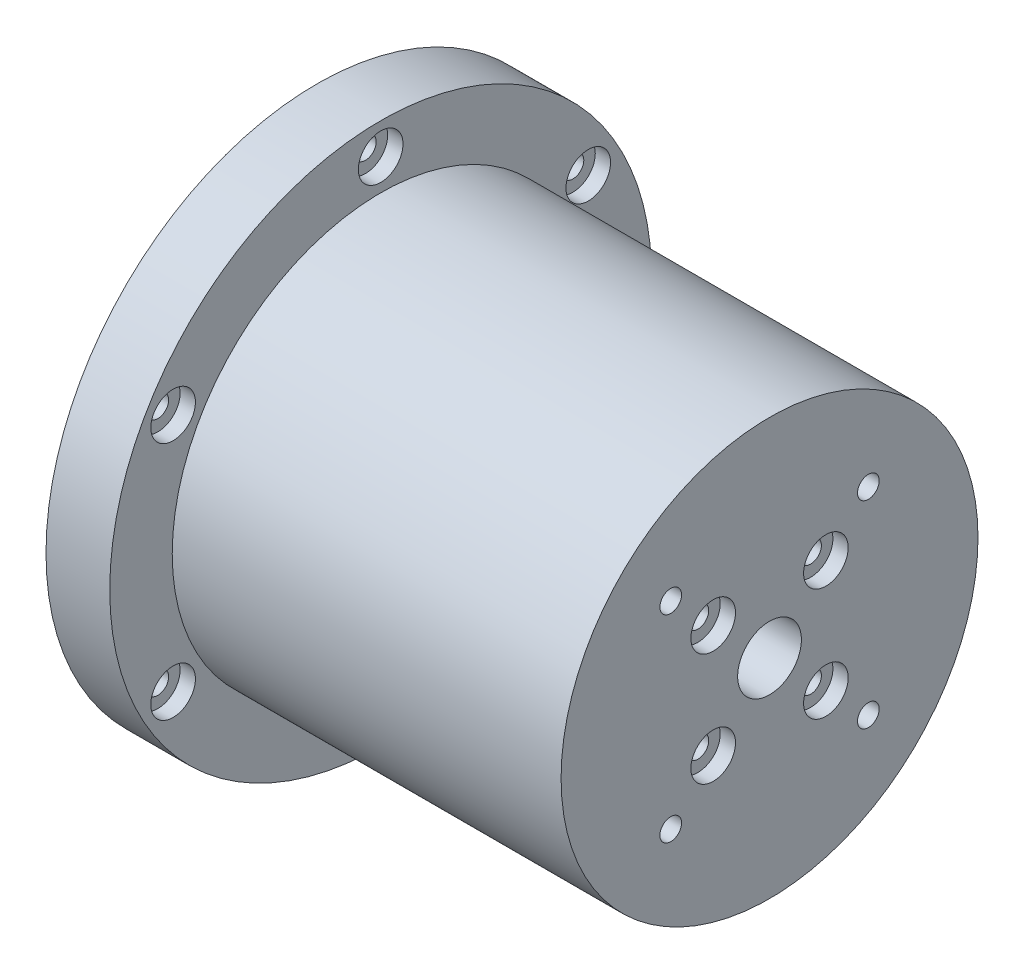
SolidWorks part; units mm, degrees
material "ABS"
ref_plane "Front" through (0, 0, 0) normal (0, 0, 1) x (1, 0, 0)
ref_plane "Top" through (0, 0, 0) normal (0, 1, 0) x (1, 0, 0)
ref_plane "Right" through (0, 0, 0) normal (1, 0, 0) x (0, 0, -1)
sketch "Croquis1" plane through (0, 0, 0) normal (1, 0, 0) x (0, 0, -1)
  circle A0 centre (0, 0) radius 32.7
  circle A1 centre (0, 0) radius 5
  dimension "D1" = 65.4
  dimension "D2" = 10
extrude "Saliente-Extruir1" add sketch "Croquis1" along normal mid plane 8.5
hole_wizard "Refrentado para tornillo con cabeza troncocónica de M31" positions "Croquis2" profile "Croquis4" counterbore size "M3" standard "Ansi Metric" end condition up to next
sketch "Croquis2" plane through (4.25, 0, 0) normal (1, 0, 0) x (0, 0, -1)
  line L1 (-8.8388, -8.8388) -> (8.8388, -8.8388) construction
  line L2 (-8.8388, -8.8388) -> (-8.8388, 8.8388) construction
  line L3 (-8.8388, 8.8388) -> (8.8388, 8.8388) construction
  line L4 (8.8388, -8.8388) -> (8.8388, 8.8388) construction
  line L5 (-8.8388, -8.8388) -> (8.8388, 8.8388) construction
  line L6 (-8.8388, 8.8388) -> (8.8388, -8.8388) construction
  point P2 (8.8388, 8.8388)
  point P25 (-8.8388, -8.8388)
  point P26 (-8.8388, 8.8388)
  point P27 (8.8388, -8.8388)
  dimension "D1" = 25
sketch "Croquis4" plane through (4.25, 8.8388, -8.8388) normal (0, 1, 0) x (0, 0, -1)
  line L0 (0, 0) -> (0, 8.5)
  line L1 (0, 8.5) -> (1.7, 8.5)
  line L3 (1.7, 8.5) -> (1.7, 2.4)
  line L4 (1.7, 2.4) -> (3.5, 2.4)
  line L5 (3.5, 2.4) -> (3.5, 0)
  line L7 (3.5, 0) -> (0, 0)
  line L11 (0, -6.35) -> (0, 107.95) construction
  dimension "Diámetro de taladro hasta el siguiente" = 3.4
  dimension "Profundidad de taladro hasta el siguiente" = 8.5
  dimension "Diámetro de refrentado" = 7
  dimension "Profundidad de refrentado" = 2.4
sketch "Croquis5" plane through (-4.25, 0, 0) normal (-1, 0, 0) x (0, 0, 1)
  circle A0 centre (0, 0) radius 21.5
  circle A1 centre (0, 0) radius 32.7 construction
  circle A2 centre (0, 0) radius 32.7
  dimension "D1" = 43
extrude "Saliente-Extruir2" add sketch "Croquis5" along normal blind 55
hole_wizard "Taladro de margen para M31" positions "Croquis6" profile "Croquis8" hole size "M3" standard "Ansi Metric"
sketch "Croquis6" plane through (-59.25, 0, 0) normal (-1, 0, 0) x (0, 0, 1)
  line L1 (-17.075, -17.075) -> (17.075, -17.075) construction
  line L2 (-17.075, -17.075) -> (-17.075, 17.075) construction
  line L3 (-17.075, 17.075) -> (17.075, 17.075) construction
  line L4 (17.075, -17.075) -> (17.075, 17.075) construction
  line L5 (-17.075, -17.075) -> (17.075, 17.075) construction
  line L6 (-17.075, 17.075) -> (17.075, -17.075) construction
  point P2 (17.075, 17.075)
  point P25 (-17.075, -17.075)
  point P26 (-17.075, 17.075)
  point P27 (17.075, -17.075)
  dimension "D1" = 34.15
sketch "Croquis8" plane through (-59.25, 17.075, 17.075) normal (0, 1, 0) x (0, 0, 1)
  line L0 (0, 0) -> (0, 16.0215)
  line L1 (0, 16.0215) -> (1.7, 15)
  line L2 (1.7, 15) -> (1.7, 0)
  line L5 (1.7, 0) -> (0, 0)
  line L10 (0, 16.0215) -> (-1.7, 15) construction
  line L11 (0, -6.35) -> (0, 107.95) construction
  dimension "Diámetro de taladro" = 3.4
  dimension "Profundidad de taladro" = 15
  dimension "Ángulo de perforador" = 118
hole_wizard "Taladro de margen para M32" positions "Croquis9" profile "Croquis10" hole size "M3" standard "Ansi Metric"
sketch "Croquis9" plane through (4.25, 0, 0) normal (1, 0, 0) x (0, 0, -1)
  line L1 (-15.5, -15.5) -> (15.5, -15.5) construction
  line L2 (-15.5, -15.5) -> (-15.5, 15.5) construction
  line L3 (-15.5, 15.5) -> (15.5, 15.5) construction
  line L4 (15.5, -15.5) -> (15.5, 15.5) construction
  line L5 (-15.5, -15.5) -> (15.5, 15.5) construction
  line L6 (-15.5, 15.5) -> (15.5, -15.5) construction
  point P2 (15.5, 15.5)
  point P13 (-15.5, -15.5)
  point P14 (-15.5, 15.5)
  point P15 (15.5, -15.5)
  dimension "D1" = 31
sketch "Croquis10" plane through (4.25, 15.5, -15.5) normal (0, 1, 0) x (0, 0, -1)
  line L0 (0, 0) -> (0, 17.5215)
  line L1 (0, 17.5215) -> (1.7, 16.5)
  line L2 (1.7, 16.5) -> (1.7, 0)
  line L5 (1.7, 0) -> (0, 0)
  line L10 (0, 17.5215) -> (-1.7, 16.5) construction
  line L11 (0, -6.35) -> (0, 107.95) construction
  dimension "Diámetro de taladro" = 3.4
  dimension "Profundidad de taladro" = 16.5
  dimension "Ángulo de perforador" = 118
sketch "Croquis12" plane through (-4.25, 0, 0) normal (-1, 0, 0) x (0, 0, 1)
  line L0 (-15.5, 15.5) -> (0, 0) construction
  line L1 (-13.2514, 13.2514) -> (-12.4284, 16.323)
  line L2 (-12.4284, 16.323) -> (-14.677, 18.5716)
  line L3 (-14.677, 18.5716) -> (-17.7486, 17.7486)
  line L4 (-17.7486, 17.7486) -> (-18.5716, 14.677)
  line L5 (-18.5716, 14.677) -> (-16.323, 12.4284)
  line L6 (-16.323, 12.4284) -> (-13.2514, 13.2514)
  line L7 (13.2514, 13.2514) -> (16.323, 12.4284)
  line L8 (16.323, 12.4284) -> (18.5716, 14.677)
  line L9 (18.5716, 14.677) -> (17.7486, 17.7486)
  line L10 (17.7486, 17.7486) -> (14.677, 18.5716)
  line L11 (14.677, 18.5716) -> (12.4284, 16.323)
  line L12 (12.4284, 16.323) -> (13.2514, 13.2514)
  line L13 (13.2514, -13.2514) -> (12.4284, -16.323)
  line L14 (12.4284, -16.323) -> (14.677, -18.5716)
  line L15 (14.677, -18.5716) -> (17.7486, -17.7486)
  line L16 (17.7486, -17.7486) -> (18.5716, -14.677)
  line L17 (18.5716, -14.677) -> (16.323, -12.4284)
  line L18 (16.323, -12.4284) -> (13.2514, -13.2514)
  line L19 (-13.2514, -13.2514) -> (-16.323, -12.4284)
  line L20 (-16.323, -12.4284) -> (-18.5716, -14.677)
  line L21 (-18.5716, -14.677) -> (-17.7486, -17.7486)
  line L22 (-17.7486, -17.7486) -> (-14.677, -18.5716)
  line L23 (-14.677, -18.5716) -> (-12.4284, -16.323)
  line L24 (-12.4284, -16.323) -> (-13.2514, -13.2514)
  circle A0 centre (-15.5, 15.5) radius 2.754 construction
  circle A1 centre (15.5, 15.5) radius 2.754 construction
  circle A2 centre (15.5, -15.5) radius 2.754 construction
  circle A3 centre (-15.5, -15.5) radius 2.754 construction
  dimension "D1" = 3.18
  dimension "D2" = 4
extrude "Cortar-Extruir1" cut sketch "Croquis12" along normal blind 4
sketch "Croquis16" plane through (-59.25, 0, 0) normal (-1, 0, 0) x (0, 0, 1)
  line L0 (17.75, 21.5) -> (21.5, 17.75)
  line L1 (-21.5, -21.5) -> (21.5, -21.5) construction
  line L2 (-21.5, -21.5) -> (-21.5, 21.5) construction
  line L3 (-21.5, 21.5) -> (21.5, 21.5) construction
  line L4 (21.5, -21.5) -> (21.5, 21.5) construction
  line L5 (-21.5, -21.5) -> (21.5, 21.5) construction
  line L6 (-21.5, 21.5) -> (21.5, -21.5) construction
  line L7 (21.5, 17.75) -> (21.5, -17.75)
  line L8 (21.5, -17.75) -> (17.75, -21.5)
  line L9 (17.75, -21.5) -> (-17.75, -21.5)
  line L10 (-17.75, -21.5) -> (-21.5, -17.75)
  line L11 (-21.5, -17.75) -> (-21.5, 17.75)
  line L12 (-21.5, 17.75) -> (-17.75, 21.5)
  line L13 (-17.75, 21.5) -> (17.75, 21.5)
  circle A0 centre (0, 0) radius 21.5 construction
  circle A1 centre (0, 0) radius 32.7
  circle A2 centre (0, 0) radius 32.7
  dimension "D2" = 3.75
  dimension "D3" = 3.75
  dimension "D1" = 0
extrude "Saliente-Extruir3" add sketch "Croquis16" along normal blind 7.5
sketch "Croquis17" plane through (-66.75, 0, 0) normal (-1, 0, 0) x (0, 0, 1)
  circle A0 centre (0, 0) radius 42.5
  circle A1 centre (0, 0) radius 32.7 construction
  circle A2 centre (0, 0) radius 32.7
  dimension "D1" = 85
extrude "Saliente-Extruir4" add sketch "Croquis17" against normal blind 10
hole_wizard "Refrentado para tornillo con cabeza troncocónica de M32" positions "Croquis18" profile "Croquis19" counterbore size "M3" standard "Ansi Metric" end condition up to next
sketch "Croquis18" plane through (-56.75, 0, 0) normal (1, 0, 0) x (0, 0, -1)
  line L0 (0, 39.05) -> (0, -39.05) construction
  line L1 (0, 42.5) -> (0, 32.7) construction
  circle A0 centre (0, 0) radius 42.5 construction
  circle A1 centre (0, 0) radius 32.7 construction
  point P0 (0, 37.6)
  point P15 (0, 37.6)
  point P20 (32.5626, 18.8)
  point P21 (32.5626, -18.8)
  point P22 (0, -37.6)
  point P23 (-32.5626, -18.8)
  point P24 (-32.5626, 18.8)
  dimension "D1" = 6
sketch "Croquis19" plane through (-56.75, 37.6, 0) normal (0, 1, 0) x (0, 0, -1)
  line L0 (0, 0) -> (0, 10)
  line L1 (0, 10) -> (1.7, 10)
  line L3 (1.7, 10) -> (1.7, 2.4)
  line L4 (1.7, 2.4) -> (3.5, 2.4)
  line L5 (3.5, 2.4) -> (3.5, 0)
  line L7 (3.5, 0) -> (0, 0)
  line L11 (0, -6.35) -> (0, 107.95) construction
  dimension "Diámetro de taladro hasta el siguiente" = 3.4
  dimension "Profundidad de taladro hasta el siguiente" = 10
  dimension "Diámetro de refrentado" = 7
  dimension "Profundidad de refrentado" = 2.4
